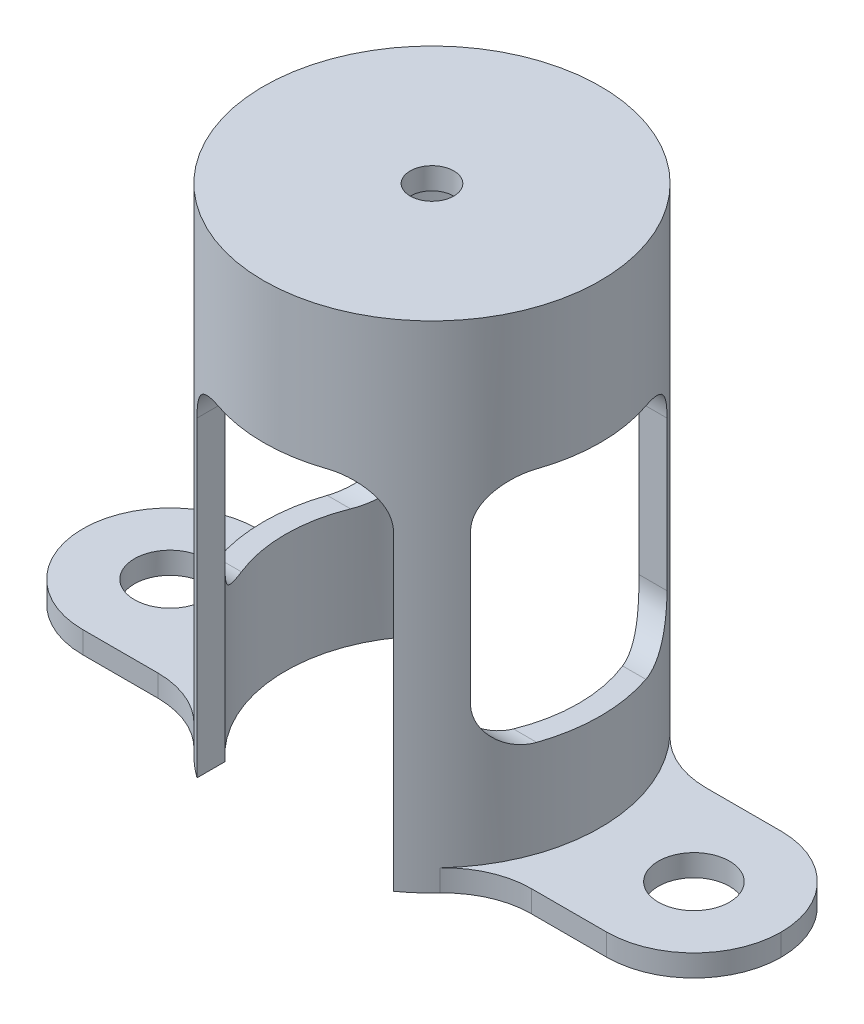
SolidWorks part; units mm, degrees
material "6061-T6 (SS)"
ref_plane "Front Plane" through (0, 0, 0) normal (0, 0, 1) x (1, 0, 0)
ref_plane "Top Plane" through (0, 0, 0) normal (0, 1, 0) x (1, 0, 0)
ref_plane "Right Plane" through (0, 0, 0) normal (1, 0, 0) x (0, 0, -1)
sketch "Sketch2" plane through (0, 0, 0) normal (0, 1, 0) x (1, 0, 0)
  circle A1 centre (0, 0) radius 7.715
  dimension "D2" = 15.43
extrude "Boss-Extrude1" add sketch "Sketch2" along normal blind 21.7
sketch "Sketch4" plane through (0, 21.7, 0) normal (0, 1, 0) x (1, 0, 0)
  circle A0 centre (0, 0) radius 1
  dimension "D1" = 2
extrude "Cut-Extrude2" cut sketch "Sketch4" against normal through all
sketch "Sketch11" plane through (0, 0, 0) normal (0, -1, 0) x (1, 0, 0)
  line L0 (6.5971, 4) -> (16, 4)
  line L1 (-16, 4) -> (-6.5971, 4)
  line L2 (-16, 4) -> (-16, -4)
  line L3 (-16, -4) -> (-6.5971, -4)
  line L4 (16, 4) -> (16, -4)
  line L5 (-16, 4) -> (16, -4) construction
  line L6 (-16, -4) -> (16, 4) construction
  line L7 (6.5971, -4) -> (16, -4)
  arc A0 (6.5971, 4) -> (-6.5971, 4) centre (0, 0) ccw
  circle A1 centre (0, 0) radius 6.715
  arc A2 (-6.5971, -4) -> (6.5971, -4) centre (0, 0) ccw
  point P0 (0, 0)
  dimension "D3" = 15.43
  dimension "D4" = 13.43
  dimension "D1" = 8
  dimension "D2" = 32
extrude "Boss-Extrude2" add sketch "Sketch11" along normal blind 1
sketch "Sketch12" plane through (0, 0, 0) normal (0, -1, 0) x (1, 0, 0)
  circle A0 centre (0, 0) radius 6.715
  dimension "D1" = 13.43
extrude "Cut-Extrude7" cut sketch "Sketch12" against normal blind 20.7
ref_plane "Plane4" through (0, 0, 30) normal (0, 0, 1) x (1, 0, 0)
sketch "Sketch13" plane through (0, 0, 30) normal (0, 0, 1) x (1, 0, 0)
  line L0 (0, -8.4865) -> (0, 8.4865) construction
  line L1 (-4.5, 15.275) -> (4.5, 15.275)
  line L2 (-4.5, 15.275) -> (-4.5, -1)
  line L3 (-4.5, -1) -> (4.5, -1)
  line L4 (4.5, 15.275) -> (4.5, -1)
  line L5 (-4.5, 15.275) -> (4.5, -1) construction
  line L6 (-4.5, -1) -> (4.5, 15.275) construction
  line L7 (-6.5971, -1) -> (6.5971, -1) construction
  point P0 (0, 7.1375)
  dimension "D1" = 16.275
  dimension "D2" = 9
extrude "Cut-Extrude8" cut sketch "Sketch13" against normal through all
ref_plane "Plane5" through (30, 0, 0) normal (1, 0, 0) x (0, 0, -1)
sketch "Sketch14" plane through (30, 0, 0) normal (1, 0, 0) x (0, 0, -1)
  line L0 (0, 12.485) -> (0, -12.485) construction
  line L1 (-4.5, 15.275) -> (4.5, 15.275)
  line L2 (-4.5, 15.275) -> (-4.5, 4.425)
  line L3 (-4.5, 4.425) -> (4.5, 4.425)
  line L4 (4.5, 15.275) -> (4.5, 4.425)
  line L5 (-4.5, 15.275) -> (4.5, 4.425) construction
  line L6 (-4.5, 4.425) -> (4.5, 15.275) construction
  line L7 (4, -1) -> (-4, -1) construction
  point P0 (0, 9.85)
  dimension "D2" = 9
  dimension "D1" = 10.85
  dimension "D3" = 10.85
extrude "Cut-Extrude9" cut sketch "Sketch14" against normal through all
fillet "Fillet3" radius 2 12 edges at (4.5, 15.275, -5.6254) (-4.5, 15.275, -5.6254) (-4.5, 15.275, 5.6254) (4.5, 15.275, 5.6254) (-5.6254, 15.275, 4.5) (-5.6254, 15.275, -4.5) (-5.6254, 4.425, -4.5) (-5.6254, 4.425, 4.5) (5.6254, 4.425, 4.5) (5.6254, 15.275, 4.5) (5.6254, 15.275, -4.5) (5.6254, 4.425, -4.5)
fillet "Fillet4" radius 4 8 edges at (6.5971, -0.5, -4) (16, -0.5, -4) (6.5971, -0.5, 4) (16, -0.5, 4) (-6.5971, -0.5, 4) (-16, -0.5, -4) (-6.5971, -0.5, -4) (-16, -0.5, 4)
sketch "Sketch15" plane through (0, 0, 0) normal (0, 1, 0) x (1, 0, 0)
  line L0 (-12.485, 0) -> (12.485, 0) construction
  circle A0 centre (-12, 0) radius 1.63
  circle A1 centre (12, 0) radius 1.63
  dimension "D3" = 3.26
  dimension "D4" = 3.26
  dimension "D1" = 12
  dimension "D2" = 12
extrude "Cut-Extrude10" cut sketch "Sketch15" against normal up to next
equation "\"FrangiboltTotalDiameter\"= .450in"
equation "\"FrangiboltTotalLength\"= .500in"
equation "\"FrangiboltThruHoleDiameter\"= .116in"
equation "\"EnclosureWallThickness\"= 1mm"
equation "\"EnclosureWallSpacing\"= 1mm"
equation "\"EnclosureInnerDiameter\"= \"FrangiboltTotalDiameter\" + 2 * \"EnclosureWallSpacing\""
equation "\"EnclosureOuterDiameter\"= \"FrangiboltTotalDiameter\" + 2 * \"EnclosureWallSpacing\" + 2 * \"EnclosureWallThickness\""
equation "\"EnclosureTotalLength\"= \"FrangiboltTotalLength\" + \"DamperLength\" + \"EnclosureWallThickness\""
equation "\"D2@Sketch2\"=\"EnclosureOuterDiameter\""
equation "\"D1@Boss-Extrude1\"=\"EnclosureTotalLength\""
equation "\"DamperLength\"= 8"
equation "\"EnclosureLip\"= 5mm"
equation "\"FrangiboltBoxWidth\"= 7mm"
equation "\"EnclosureMountingStandoff\"= 32mm"
equation "\"D2@Sketch11\"=\"EnclosureMountingStandoff\""
equation "\"D3@Sketch11\"=\"EnclosureOuterDiameter\""
equation "\"D4@Sketch11\"=\"EnclosureInnerDiameter\""
equation "\"D1@Boss-Extrude2\"=\"EnclosureWallThickness\""
equation "\"D1@Sketch12\"=\"EnclosureInnerDiameter\""
equation "\"D1@Cut-Extrude7\"=\"EnclosureTotalLength\"-\"EnclosureWallThickness\""
equation "\"D1@Sketch13\"=\"EnclosureTotalLength\"*0.75"
equation "\"D2@Sketch13\"=\"FrangiboltBoxWidth\"+2mm"
equation "\"D1@Sketch14\"=\"EnclosureTotalLength\"*0.5"
equation "\"D2@Sketch14\"=\"FrangiboltBoxWidth\"+2mm"
equation "\"D3@Sketch14\"=\"EnclosureTotalLength\"*0.5"
equation "\"EnclosureMountingHoleDiameter\"= 3.26mm"
equation "\"D3@Sketch15\"=\"EnclosureMountingHoleDiameter\""
equation "\"D4@Sketch15\"=\"EnclosureMountingHoleDiameter\""
